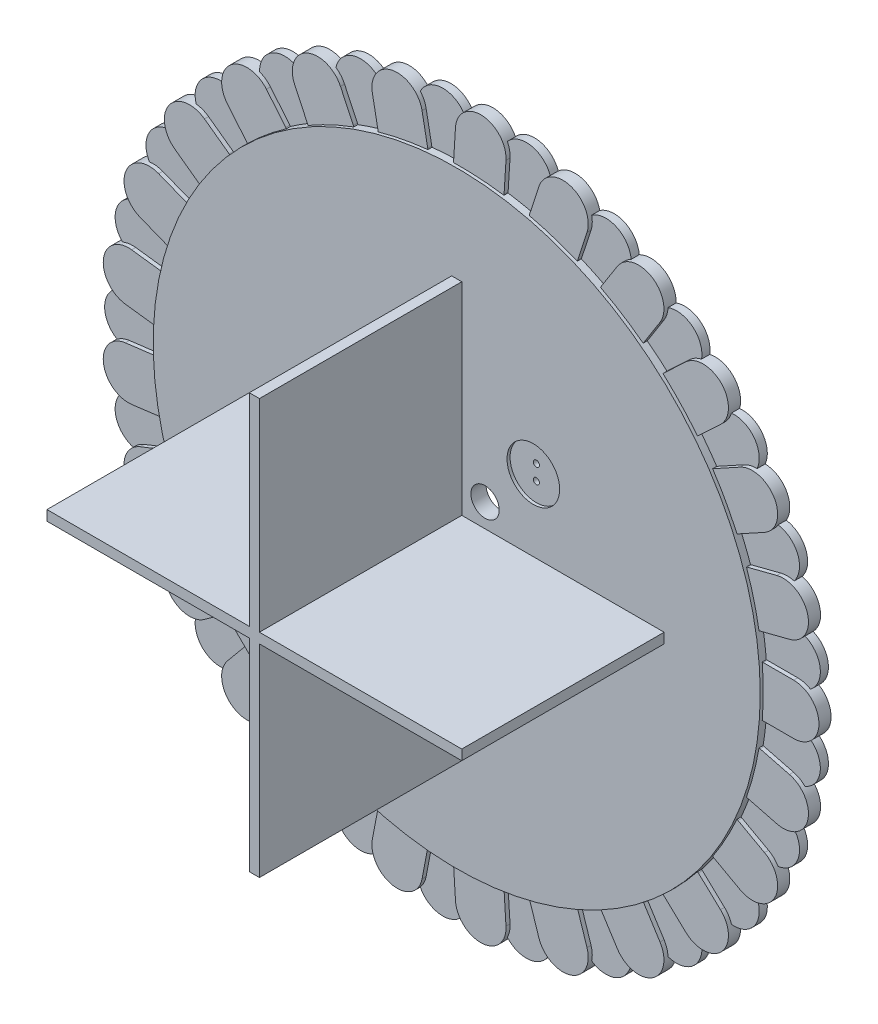
SolidWorks part; units mm, degrees
ref_plane "Front Plane" through (0, 0, 0) normal (0, 0, 1) x (1, 0, 0)
ref_plane "Top Plane" through (0, 0, 0) normal (0, 1, 0) x (1, 0, 0)
ref_plane "Right Plane" through (0, 0, 0) normal (1, 0, 0) x (0, 0, -1)
sketch "Schizzo1" plane through (0, 0, 0) normal (0, 0, 1) x (1, 0, 0)
  circle A0 centre (0, 0) radius 30
  dimension "D1" = 60
extrude "Estrusione-Estrusione1" add sketch "Schizzo1" along normal blind 1.5
sketch "Schizzo2" plane through (0, 0, 1.5) normal (0, 0, 1) x (1, 0, 0)
  line L0 (-0.5, 0.5) -> (-0.5, 20.5)
  line L1 (-20.5, 0.5) -> (-0.5, 0.5)
  line L2 (-20.5, 0.5) -> (-20.5, -0.5)
  line L3 (-20.5, -0.5) -> (-0.5, -0.5)
  line L4 (20.5, 0.5) -> (20.5, -0.5)
  line L5 (-0.5, 0.5) -> (0.5, -0.5) construction
  line L7 (0.5, -20.5) -> (-0.5, -20.5)
  line L8 (0.5, -20.5) -> (0.5, -0.5)
  line L9 (0.5, 20.5) -> (-0.5, 20.5)
  line L10 (-0.5, -20.5) -> (-0.5, -0.5)
  line L15 (0.5, 0.5) -> (0.5, 20.5)
  line L18 (0.5, 0.5) -> (20.5, 0.5)
  line L19 (0.5, -0.5) -> (20.5, -0.5)
  point P0 (0, 0)
  point P6 (0, 0)
  point P11 (0, 0)
  dimension "D1" = 20
  dimension "D2" = 1
extrude "Estrusione-Estrusione2" add sketch "Schizzo2" along normal blind 20
sketch "Schizzo3" plane through (0, 0, 1.5) normal (0, 0, 1) x (1, 0, 0)
  line L0 (-7.5711, 6.8211) -> (-7.5711, 8.3211) construction
  line L1 (-20.5, 0) -> (20.5, 0) construction
  line L2 (0.2363, -0.2363) -> (-0.5137, 0.5137) construction
  line L4 (-20.5, 0.5) -> (-20.5, -0.5) construction
  line L5 (20.5, -0.5) -> (20.5, 0.5) construction
  line L6 (0.5, 20.5) -> (-0.5, 20.5) construction
  line L7 (0, 20.5) -> (0, -20.5) construction
  line L8 (-0.5, -20.5) -> (0.5, -20.5) construction
  circle A0 centre (-7.5711, 8.3211) radius 0.3
  circle A1 centre (-7.5711, 6.8211) radius 0.3
  circle A3 centre (-7.5711, 7.5711) radius 2.5 construction
  circle A4 centre (-7.5711, -8.3211) radius 0.3
  circle A5 centre (-7.5711, -6.8211) radius 0.3
  circle A6 centre (-7.5711, -7.5711) radius 2.5 construction
  circle A7 centre (7.5711, -8.3211) radius 0.3
  circle A8 centre (7.5711, -7.5711) radius 2.5 construction
  circle A9 centre (7.5711, -6.8211) radius 0.3
  circle A10 centre (7.5711, 8.3211) radius 0.3
  circle A11 centre (7.5711, 6.8211) radius 0.3
  circle A12 centre (7.5711, 7.5711) radius 2.5 construction
  dimension "D1" = 1.5
  dimension "D2" = 0.6
  dimension "D3" = 5
  dimension "D4" = 10
extrude "Taglio-Estrusione1" cut sketch "Schizzo3" against normal through all contours A1 | A0 | A11 | A10 | A5 | A4 | A7 | A9 region at (-7.5711, 8.3211, 1.5) region at (-7.5711, 6.8211, 1.5) region at (-7.5711, -8.3211, 1.5) region at (-7.5711, -6.8211, 1.5) region at (7.5711, -8.3211, 1.5) region at (7.5711, -6.8211, 1.5) region at (7.5711, 8.3211, 1.5) region at (7.5711, 6.8211, 1.5)
sketch "Schizzo4" plane through (0, 0, 1.5) normal (0, 0, 1) x (1, 0, 0)
  line L0 (-7.5711, -6.8211) -> (-7.5711, -8.3211) construction
  line L1 (-20.5, 0) -> (-4.4705, 0) construction
  line L2 (-20.5, 0.5) -> (-20.5, -0.5) construction
  line L3 (0, -20.5) -> (0, -5.0355) construction
  line L4 (-0.5, -20.5) -> (0.5, -20.5) construction
  circle A0 centre (-7.5711, -7.5711) radius 2.6
  circle A1 centre (7.5711, -7.5711) radius 2.6
  circle A2 centre (7.5711, 7.5711) radius 2.6
  circle A3 centre (-7.5711, 7.5711) radius 2.6
  dimension "D1" = 5.2
extrude "Taglio-Estrusione2" cut sketch "Schizzo4" against normal blind 0.3
sketch "Schizzo5" plane through (0, 0, 0) normal (0, 0, -1) x (-1, 0, 0)
  line L0 (-30, 0) -> (-33, 0) construction
  line L1 (-30, -2.5) -> (-33, -2.5)
  line L2 (-30, 2.5) -> (-33, 2.5)
  line L3 (-29.4501, 6.2403) -> (-32.4265, 6.6163)
  line L4 (-30.0768, 1.2797) -> (-33.0531, 1.6557)
  line L5 (-29.7634, 3.76) -> (-32.7398, 4.136) construction
  line L6 (-28.4358, 9.8822) -> (-31.3415, 10.6282)
  line L7 (-29.6792, 5.0392) -> (-32.585, 5.7853)
  line L8 (-29.0575, 7.4607) -> (-31.9632, 8.2068) construction
  line L9 (-26.973, 13.3682) -> (-29.7623, 14.4726)
  line L10 (-28.8136, 8.7193) -> (-31.6029, 9.8237)
  line L11 (-27.8933, 11.0437) -> (-30.6826, 12.1481) construction
  line L12 (-25.0848, 16.6434) -> (-27.7137, 18.0886)
  line L13 (-27.4936, 12.2618) -> (-30.1225, 13.7071)
  line L14 (-26.2892, 14.4526) -> (-28.9181, 15.8979) construction
  line L15 (-22.801, 19.6561) -> (-25.2281, 21.4195)
  line L16 (-25.74, 15.611) -> (-28.167, 17.3744)
  line L17 (-24.2705, 17.6336) -> (-26.6976, 19.3969) construction
  line L18 (-20.1577, 22.3588) -> (-22.3446, 24.4125)
  line L19 (-23.5804, 18.714) -> (-25.7673, 20.7676)
  line L20 (-21.8691, 20.5364) -> (-24.056, 22.5901) construction
  line L21 (-17.1964, 24.709) -> (-19.1087, 27.0205)
  line L22 (-21.049, 21.5218) -> (-22.9613, 23.8334)
  line L23 (-19.1227, 23.1154) -> (-21.035, 25.4269) construction
  line L24 (-13.964, 26.6694) -> (-15.5715, 29.2024)
  line L25 (-18.1856, 23.9903) -> (-19.7931, 26.5233)
  line L26 (-16.0748, 25.3298) -> (-17.6823, 27.8628) construction
  line L27 (-10.5113, 28.2093) -> (-11.7886, 30.9237)
  line L28 (-15.0354, 26.0804) -> (-16.3128, 28.7948)
  line L29 (-12.7734, 27.1448) -> (-14.0507, 29.8593) construction
  line L30 (-6.8929, 29.3042) -> (-7.8199, 32.1574)
  line L31 (-11.6482, 27.7592) -> (-12.5752, 30.6123)
  line L32 (-9.2705, 28.5317) -> (-10.1976, 31.3849) construction
  line L33 (-3.1657, 29.9371) -> (-3.7279, 32.8839)
  line L34 (-8.0772, 29.0002) -> (-8.6393, 31.947)
  line L35 (-5.6214, 29.4686) -> (-6.1836, 32.4155) construction
  line L36 (0.6114, 30.0978) -> (0.423, 33.0919)
  line L37 (-4.3788, 29.7838) -> (-4.5672, 32.7779)
  line L38 (-1.8837, 29.9408) -> (-2.0721, 32.9349) construction
  line L39 (4.3788, 29.7838) -> (4.5672, 32.7779)
  line L40 (-0.6114, 30.0978) -> (-0.423, 33.0919)
  line L41 (1.8837, 29.9408) -> (2.0721, 32.9349) construction
  line L42 (8.0772, 29.0002) -> (8.6393, 31.947)
  line L43 (3.1657, 29.9371) -> (3.7279, 32.8839)
  line L44 (5.6214, 29.4686) -> (6.1836, 32.4155) construction
  line L45 (11.6482, 27.7592) -> (12.5752, 30.6123)
  line L46 (6.8929, 29.3042) -> (7.8199, 32.1574)
  line L47 (9.2705, 28.5317) -> (10.1976, 31.3849) construction
  line L48 (15.0354, 26.0804) -> (16.3128, 28.7948)
  line L49 (10.5113, 28.2093) -> (11.7886, 30.9237)
  line L50 (12.7734, 27.1448) -> (14.0507, 29.8593) construction
  line L51 (18.1856, 23.9903) -> (19.7931, 26.5233)
  line L52 (13.964, 26.6694) -> (15.5715, 29.2024)
  line L53 (16.0748, 25.3298) -> (17.6823, 27.8628) construction
  line L54 (21.049, 21.5218) -> (22.9613, 23.8334)
  line L55 (17.1964, 24.709) -> (19.1087, 27.0205)
  line L56 (19.1227, 23.1154) -> (21.035, 25.4269) construction
  line L57 (23.5804, 18.714) -> (25.7673, 20.7676)
  line L58 (20.1577, 22.3588) -> (22.3446, 24.4125)
  line L59 (21.8691, 20.5364) -> (24.056, 22.5901) construction
  line L60 (25.74, 15.611) -> (28.167, 17.3744)
  line L61 (22.801, 19.6561) -> (25.2281, 21.4195)
  line L62 (24.2705, 17.6336) -> (26.6976, 19.3969) construction
  line L63 (27.4936, 12.2618) -> (30.1225, 13.7071)
  line L64 (25.0848, 16.6434) -> (27.7137, 18.0886)
  line L65 (26.2892, 14.4526) -> (28.9181, 15.8979) construction
  line L66 (28.8136, 8.7193) -> (31.6029, 9.8237)
  line L67 (26.973, 13.3682) -> (29.7623, 14.4726)
  line L68 (27.8933, 11.0437) -> (30.6826, 12.1481) construction
  line L69 (29.6792, 5.0392) -> (32.585, 5.7853)
  line L70 (28.4358, 9.8822) -> (31.3415, 10.6282)
  line L71 (29.0575, 7.4607) -> (31.9632, 8.2068) construction
  line L72 (30.0768, 1.2797) -> (33.0531, 1.6557)
  line L73 (29.4501, 6.2403) -> (32.4265, 6.6163)
  line L74 (29.7634, 3.76) -> (32.7398, 4.136) construction
  line L75 (30, -2.5) -> (33, -2.5)
  line L76 (30, 2.5) -> (33, 2.5)
  line L77 (30, 0) -> (33, 0) construction
  line L78 (29.4501, -6.2403) -> (32.4265, -6.6163)
  line L79 (30.0768, -1.2797) -> (33.0531, -1.6557)
  line L80 (29.7634, -3.76) -> (32.7398, -4.136) construction
  line L81 (28.4358, -9.8822) -> (31.3415, -10.6282)
  line L82 (29.6792, -5.0392) -> (32.585, -5.7853)
  line L83 (29.0575, -7.4607) -> (31.9632, -8.2068) construction
  line L84 (26.973, -13.3682) -> (29.7623, -14.4726)
  line L85 (28.8136, -8.7193) -> (31.6029, -9.8237)
  line L86 (27.8933, -11.0437) -> (30.6826, -12.1481) construction
  line L87 (25.0848, -16.6434) -> (27.7137, -18.0886)
  line L88 (27.4936, -12.2618) -> (30.1225, -13.7071)
  line L89 (26.2892, -14.4526) -> (28.9181, -15.8979) construction
  line L90 (22.801, -19.6561) -> (25.2281, -21.4195)
  line L91 (25.74, -15.611) -> (28.167, -17.3744)
  line L92 (24.2705, -17.6336) -> (26.6976, -19.3969) construction
  line L93 (20.1577, -22.3588) -> (22.3446, -24.4125)
  line L94 (23.5804, -18.714) -> (25.7673, -20.7676)
  line L95 (21.8691, -20.5364) -> (24.056, -22.5901) construction
  line L96 (17.1964, -24.709) -> (19.1087, -27.0205)
  line L97 (21.049, -21.5218) -> (22.9613, -23.8334)
  line L98 (19.1227, -23.1154) -> (21.035, -25.4269) construction
  line L99 (13.964, -26.6694) -> (15.5715, -29.2024)
  line L100 (18.1856, -23.9903) -> (19.7931, -26.5233)
  line L101 (16.0748, -25.3298) -> (17.6823, -27.8628) construction
  line L102 (10.5113, -28.2093) -> (11.7886, -30.9237)
  line L103 (15.0354, -26.0804) -> (16.3128, -28.7948)
  line L104 (12.7734, -27.1448) -> (14.0507, -29.8593) construction
  line L105 (6.8929, -29.3042) -> (7.8199, -32.1574)
  line L106 (11.6482, -27.7592) -> (12.5752, -30.6123)
  line L107 (9.2705, -28.5317) -> (10.1976, -31.3849) construction
  line L108 (3.1657, -29.9371) -> (3.7279, -32.8839)
  line L109 (8.0772, -29.0002) -> (8.6393, -31.947)
  line L110 (5.6214, -29.4686) -> (6.1836, -32.4155) construction
  line L111 (-0.6114, -30.0978) -> (-0.423, -33.0919)
  line L112 (4.3788, -29.7838) -> (4.5672, -32.7779)
  line L113 (1.8837, -29.9408) -> (2.0721, -32.9349) construction
  line L114 (-4.3788, -29.7838) -> (-4.5672, -32.7779)
  line L115 (0.6114, -30.0978) -> (0.423, -33.0919)
  line L116 (-1.8837, -29.9408) -> (-2.0721, -32.9349) construction
  line L117 (-8.0772, -29.0002) -> (-8.6393, -31.947)
  line L118 (-3.1657, -29.9371) -> (-3.7279, -32.8839)
  line L119 (-5.6214, -29.4686) -> (-6.1836, -32.4155) construction
  line L120 (-11.6482, -27.7592) -> (-12.5752, -30.6123)
  line L121 (-6.8929, -29.3042) -> (-7.8199, -32.1574)
  line L122 (-9.2705, -28.5317) -> (-10.1976, -31.3849) construction
  line L123 (-15.0354, -26.0804) -> (-16.3128, -28.7948)
  line L124 (-10.5113, -28.2093) -> (-11.7886, -30.9237)
  line L125 (-12.7734, -27.1448) -> (-14.0507, -29.8593) construction
  line L126 (-18.1856, -23.9903) -> (-19.7931, -26.5233)
  line L127 (-13.964, -26.6694) -> (-15.5715, -29.2024)
  line L128 (-16.0748, -25.3298) -> (-17.6823, -27.8628) construction
  line L129 (-21.049, -21.5218) -> (-22.9613, -23.8334)
  line L130 (-17.1964, -24.709) -> (-19.1087, -27.0205)
  line L131 (-19.1227, -23.1154) -> (-21.035, -25.4269) construction
  line L132 (-23.5804, -18.714) -> (-25.7673, -20.7676)
  line L133 (-20.1577, -22.3588) -> (-22.3446, -24.4125)
  line L134 (-21.8691, -20.5364) -> (-24.056, -22.5901) construction
  line L135 (-25.74, -15.611) -> (-28.167, -17.3744)
  line L136 (-22.801, -19.6561) -> (-25.2281, -21.4195)
  line L137 (-24.2705, -17.6336) -> (-26.6976, -19.3969) construction
  line L138 (-27.4936, -12.2618) -> (-30.1225, -13.7071)
  line L139 (-25.0848, -16.6434) -> (-27.7137, -18.0886)
  line L140 (-26.2892, -14.4526) -> (-28.9181, -15.8979) construction
  line L141 (-28.8136, -8.7193) -> (-31.6029, -9.8237)
  line L142 (-26.973, -13.3682) -> (-29.7623, -14.4726)
  line L143 (-27.8933, -11.0437) -> (-30.6826, -12.1481) construction
  line L144 (-29.6792, -5.0392) -> (-32.585, -5.7853)
  line L145 (-28.4358, -9.8822) -> (-31.3415, -10.6282)
  line L146 (-29.0575, -7.4607) -> (-31.9632, -8.2068) construction
  line L147 (-30.0768, -1.2797) -> (-33.0531, -1.6557)
  line L148 (-29.4501, -6.2403) -> (-32.4265, -6.6163)
  line L149 (-29.7634, -3.76) -> (-32.7398, -4.136) construction
  circle A0 centre (0, 0) radius 30 construction
  arc A1 (-30, -2.5) -> (-30, 2.5) centre (-30, 0) ccw
  arc A2 (-33, 2.5) -> (-33, -2.5) centre (-33, 0) ccw
  arc A3 (-30.0768, 1.2797) -> (-29.4501, 6.2403) centre (-29.7634, 3.76) ccw
  arc A4 (-32.4265, 6.6163) -> (-33.0531, 1.6557) centre (-32.7398, 4.136) ccw
  arc A5 (-29.6792, 5.0392) -> (-28.4358, 9.8822) centre (-29.0575, 7.4607) ccw
  arc A6 (-31.3415, 10.6282) -> (-32.585, 5.7853) centre (-31.9632, 8.2068) ccw
  arc A7 (-28.8136, 8.7193) -> (-26.973, 13.3682) centre (-27.8933, 11.0437) ccw
  arc A8 (-29.7623, 14.4726) -> (-31.6029, 9.8237) centre (-30.6826, 12.1481) ccw
  arc A9 (-27.4936, 12.2618) -> (-25.0848, 16.6434) centre (-26.2892, 14.4526) ccw
  arc A10 (-27.7137, 18.0886) -> (-30.1225, 13.7071) centre (-28.9181, 15.8979) ccw
  arc A11 (-25.74, 15.611) -> (-22.801, 19.6561) centre (-24.2705, 17.6336) ccw
  arc A12 (-25.2281, 21.4195) -> (-28.167, 17.3744) centre (-26.6976, 19.3969) ccw
  arc A13 (-23.5804, 18.714) -> (-20.1577, 22.3588) centre (-21.8691, 20.5364) ccw
  arc A14 (-22.3446, 24.4125) -> (-25.7673, 20.7676) centre (-24.056, 22.5901) ccw
  arc A15 (-21.049, 21.5218) -> (-17.1964, 24.709) centre (-19.1227, 23.1154) ccw
  arc A16 (-19.1087, 27.0205) -> (-22.9613, 23.8334) centre (-21.035, 25.4269) ccw
  arc A17 (-18.1856, 23.9903) -> (-13.964, 26.6694) centre (-16.0748, 25.3298) ccw
  arc A18 (-15.5715, 29.2024) -> (-19.7931, 26.5233) centre (-17.6823, 27.8628) ccw
  arc A19 (-15.0354, 26.0804) -> (-10.5113, 28.2093) centre (-12.7734, 27.1448) ccw
  arc A20 (-11.7886, 30.9237) -> (-16.3128, 28.7948) centre (-14.0507, 29.8593) ccw
  arc A21 (-11.6482, 27.7592) -> (-6.8929, 29.3042) centre (-9.2705, 28.5317) ccw
  arc A22 (-7.8199, 32.1574) -> (-12.5752, 30.6123) centre (-10.1976, 31.3849) ccw
  arc A23 (-8.0772, 29.0002) -> (-3.1657, 29.9371) centre (-5.6214, 29.4686) ccw
  arc A24 (-3.7279, 32.8839) -> (-8.6393, 31.947) centre (-6.1836, 32.4155) ccw
  arc A25 (-4.3788, 29.7838) -> (0.6114, 30.0978) centre (-1.8837, 29.9408) ccw
  arc A26 (0.423, 33.0919) -> (-4.5672, 32.7779) centre (-2.0721, 32.9349) ccw
  arc A27 (-0.6114, 30.0978) -> (4.3788, 29.7838) centre (1.8837, 29.9408) ccw
  arc A28 (4.5672, 32.7779) -> (-0.423, 33.0919) centre (2.0721, 32.9349) ccw
  arc A29 (3.1657, 29.9371) -> (8.0772, 29.0002) centre (5.6214, 29.4686) ccw
  arc A30 (8.6393, 31.947) -> (3.7279, 32.8839) centre (6.1836, 32.4155) ccw
  arc A31 (6.8929, 29.3042) -> (11.6482, 27.7592) centre (9.2705, 28.5317) ccw
  arc A32 (12.5752, 30.6123) -> (7.8199, 32.1574) centre (10.1976, 31.3849) ccw
  arc A33 (10.5113, 28.2093) -> (15.0354, 26.0804) centre (12.7734, 27.1448) ccw
  arc A34 (16.3128, 28.7948) -> (11.7886, 30.9237) centre (14.0507, 29.8593) ccw
  arc A35 (13.964, 26.6694) -> (18.1856, 23.9903) centre (16.0748, 25.3298) ccw
  arc A36 (19.7931, 26.5233) -> (15.5715, 29.2024) centre (17.6823, 27.8628) ccw
  arc A37 (17.1964, 24.709) -> (21.049, 21.5218) centre (19.1227, 23.1154) ccw
  arc A38 (22.9613, 23.8334) -> (19.1087, 27.0205) centre (21.035, 25.4269) ccw
  arc A39 (20.1577, 22.3588) -> (23.5804, 18.714) centre (21.8691, 20.5364) ccw
  arc A40 (25.7673, 20.7676) -> (22.3446, 24.4125) centre (24.056, 22.5901) ccw
  arc A41 (22.801, 19.6561) -> (25.74, 15.611) centre (24.2705, 17.6336) ccw
  arc A42 (28.167, 17.3744) -> (25.2281, 21.4195) centre (26.6976, 19.3969) ccw
  arc A43 (25.0848, 16.6434) -> (27.4936, 12.2618) centre (26.2892, 14.4526) ccw
  arc A44 (30.1225, 13.7071) -> (27.7137, 18.0886) centre (28.9181, 15.8979) ccw
  arc A45 (26.973, 13.3682) -> (28.8136, 8.7193) centre (27.8933, 11.0437) ccw
  arc A46 (31.6029, 9.8237) -> (29.7623, 14.4726) centre (30.6826, 12.1481) ccw
  arc A47 (28.4358, 9.8822) -> (29.6792, 5.0392) centre (29.0575, 7.4607) ccw
  arc A48 (32.585, 5.7853) -> (31.3415, 10.6282) centre (31.9632, 8.2068) ccw
  arc A49 (29.4501, 6.2403) -> (30.0768, 1.2797) centre (29.7634, 3.76) ccw
  arc A50 (33.0531, 1.6557) -> (32.4265, 6.6163) centre (32.7398, 4.136) ccw
  arc A51 (30, 2.5) -> (30, -2.5) centre (30, 0) ccw
  arc A52 (33, -2.5) -> (33, 2.5) centre (33, 0) ccw
  arc A53 (30.0768, -1.2797) -> (29.4501, -6.2403) centre (29.7634, -3.76) ccw
  arc A54 (32.4265, -6.6163) -> (33.0531, -1.6557) centre (32.7398, -4.136) ccw
  arc A55 (29.6792, -5.0392) -> (28.4358, -9.8822) centre (29.0575, -7.4607) ccw
  arc A56 (31.3415, -10.6282) -> (32.585, -5.7853) centre (31.9632, -8.2068) ccw
  arc A57 (28.8136, -8.7193) -> (26.973, -13.3682) centre (27.8933, -11.0437) ccw
  arc A58 (29.7623, -14.4726) -> (31.6029, -9.8237) centre (30.6826, -12.1481) ccw
  arc A59 (27.4936, -12.2618) -> (25.0848, -16.6434) centre (26.2892, -14.4526) ccw
  arc A60 (27.7137, -18.0886) -> (30.1225, -13.7071) centre (28.9181, -15.8979) ccw
  arc A61 (25.74, -15.611) -> (22.801, -19.6561) centre (24.2705, -17.6336) ccw
  arc A62 (25.2281, -21.4195) -> (28.167, -17.3744) centre (26.6976, -19.3969) ccw
  arc A63 (23.5804, -18.714) -> (20.1577, -22.3588) centre (21.8691, -20.5364) ccw
  arc A64 (22.3446, -24.4125) -> (25.7673, -20.7676) centre (24.056, -22.5901) ccw
  arc A65 (21.049, -21.5218) -> (17.1964, -24.709) centre (19.1227, -23.1154) ccw
  arc A66 (19.1087, -27.0205) -> (22.9613, -23.8334) centre (21.035, -25.4269) ccw
  arc A67 (18.1856, -23.9903) -> (13.964, -26.6694) centre (16.0748, -25.3298) ccw
  arc A68 (15.5715, -29.2024) -> (19.7931, -26.5233) centre (17.6823, -27.8628) ccw
  arc A69 (15.0354, -26.0804) -> (10.5113, -28.2093) centre (12.7734, -27.1448) ccw
  arc A70 (11.7886, -30.9237) -> (16.3128, -28.7948) centre (14.0507, -29.8593) ccw
  arc A71 (11.6482, -27.7592) -> (6.8929, -29.3042) centre (9.2705, -28.5317) ccw
  arc A72 (7.8199, -32.1574) -> (12.5752, -30.6123) centre (10.1976, -31.3849) ccw
  arc A73 (8.0772, -29.0002) -> (3.1657, -29.9371) centre (5.6214, -29.4686) ccw
  arc A74 (3.7279, -32.8839) -> (8.6393, -31.947) centre (6.1836, -32.4155) ccw
  arc A75 (4.3788, -29.7838) -> (-0.6114, -30.0978) centre (1.8837, -29.9408) ccw
  arc A76 (-0.423, -33.0919) -> (4.5672, -32.7779) centre (2.0721, -32.9349) ccw
  arc A77 (0.6114, -30.0978) -> (-4.3788, -29.7838) centre (-1.8837, -29.9408) ccw
  arc A78 (-4.5672, -32.7779) -> (0.423, -33.0919) centre (-2.0721, -32.9349) ccw
  arc A79 (-3.1657, -29.9371) -> (-8.0772, -29.0002) centre (-5.6214, -29.4686) ccw
  arc A80 (-8.6393, -31.947) -> (-3.7279, -32.8839) centre (-6.1836, -32.4155) ccw
  arc A81 (-6.8929, -29.3042) -> (-11.6482, -27.7592) centre (-9.2705, -28.5317) ccw
  arc A82 (-12.5752, -30.6123) -> (-7.8199, -32.1574) centre (-10.1976, -31.3849) ccw
  arc A83 (-10.5113, -28.2093) -> (-15.0354, -26.0804) centre (-12.7734, -27.1448) ccw
  arc A84 (-16.3128, -28.7948) -> (-11.7886, -30.9237) centre (-14.0507, -29.8593) ccw
  arc A85 (-13.964, -26.6694) -> (-18.1856, -23.9903) centre (-16.0748, -25.3298) ccw
  arc A86 (-19.7931, -26.5233) -> (-15.5715, -29.2024) centre (-17.6823, -27.8628) ccw
  arc A87 (-17.1964, -24.709) -> (-21.049, -21.5218) centre (-19.1227, -23.1154) ccw
  arc A88 (-22.9613, -23.8334) -> (-19.1087, -27.0205) centre (-21.035, -25.4269) ccw
  arc A89 (-20.1577, -22.3588) -> (-23.5804, -18.714) centre (-21.8691, -20.5364) ccw
  arc A90 (-25.7673, -20.7676) -> (-22.3446, -24.4125) centre (-24.056, -22.5901) ccw
  arc A91 (-22.801, -19.6561) -> (-25.74, -15.611) centre (-24.2705, -17.6336) ccw
  arc A92 (-28.167, -17.3744) -> (-25.2281, -21.4195) centre (-26.6976, -19.3969) ccw
  arc A93 (-25.0848, -16.6434) -> (-27.4936, -12.2618) centre (-26.2892, -14.4526) ccw
  arc A94 (-30.1225, -13.7071) -> (-27.7137, -18.0886) centre (-28.9181, -15.8979) ccw
  arc A95 (-26.973, -13.3682) -> (-28.8136, -8.7193) centre (-27.8933, -11.0437) ccw
  arc A96 (-31.6029, -9.8237) -> (-29.7623, -14.4726) centre (-30.6826, -12.1481) ccw
  arc A97 (-28.4358, -9.8822) -> (-29.6792, -5.0392) centre (-29.0575, -7.4607) ccw
  arc A98 (-32.585, -5.7853) -> (-31.3415, -10.6282) centre (-31.9632, -8.2068) ccw
  arc A99 (-29.4501, -6.2403) -> (-30.0768, -1.2797) centre (-29.7634, -3.76) ccw
  arc A100 (-33.0531, -1.6557) -> (-32.4265, -6.6163) centre (-32.7398, -4.136) ccw
  point P6 (-31.5, 0)
  point P11 (0, 0)
  point P12 (0, 0)
  point P16 (-31.2516, 3.948)
  point P23 (-30.5104, 7.8337)
  point P30 (-29.288, 11.5959)
  point P37 (-27.6037, 15.1752)
  point P44 (-25.484, 18.5152)
  point P51 (-22.9625, 21.5632)
  point P58 (-20.0789, 24.2712)
  point P65 (-16.8785, 26.5963)
  point P72 (-13.412, 28.5021)
  point P79 (-9.734, 29.9583)
  point P86 (-5.9025, 30.942)
  point P93 (-1.9779, 31.4378)
  point P100 (1.9779, 31.4378)
  point P107 (5.9025, 30.942)
  point P114 (9.734, 29.9583)
  point P121 (13.412, 28.5021)
  point P128 (16.8785, 26.5963)
  point P135 (20.0789, 24.2712)
  point P142 (22.9625, 21.5632)
  point P149 (25.484, 18.5152)
  point P156 (27.6037, 15.1752)
  point P163 (29.288, 11.5959)
  point P170 (30.5104, 7.8337)
  point P177 (31.2516, 3.948)
  point P184 (31.5, 0)
  point P191 (31.2516, -3.948)
  point P198 (30.5104, -7.8337)
  point P205 (29.288, -11.5959)
  point P212 (27.6037, -15.1752)
  point P219 (25.484, -18.5152)
  point P226 (22.9625, -21.5632)
  point P233 (20.0789, -24.2712)
  point P240 (16.8785, -26.5963)
  point P247 (13.412, -28.5021)
  point P254 (9.734, -29.9583)
  point P261 (5.9025, -30.942)
  point P268 (1.9779, -31.4378)
  point P275 (-1.9779, -31.4378)
  point P282 (-5.9025, -30.942)
  point P289 (-9.734, -29.9583)
  point P296 (-13.412, -28.5021)
  point P303 (-16.8785, -26.5963)
  point P310 (-20.0789, -24.2712)
  point P317 (-22.9625, -21.5632)
  point P324 (-25.484, -18.5152)
  point P331 (-27.6037, -15.1752)
  point P338 (-29.288, -11.5959)
  point P345 (-30.5104, -7.8337)
  point P352 (-31.2516, -3.948)
  point P357 (0, 0)
  circle M206 centre (0, 0) radius 30
  dimension "D1" = 5
  dimension "D2" = 3
  dimension "D4" = 4.136
  dimension "D5" = 0.2602
  dimension "D3" = 50
extrude "Estrusione-Estrusione3" add sketch "Schizzo5" against normal blind 0.8 contours A6 A4 A2 L2 A1 A5 L7 M206 | A10 A8 A6 L6 A5 A9 L13 M206 | A14 A12 A10 L12 A9 A13 L19 M206 | A18 A16 A14 L18 A13 A17 L25 M206 | A22 A20 A18 L24 A17 A21 L31 M206 | A26 A24 A22 L30 A21 A25 L37 M206 | A30 A28 A26 L36 A25 A29 L43 M206 | A34 A32 A30 L42 A29 A33 L49 M206 | A38 A36 A34 L48 A33 A37 L55 M206 | A42 A40 A38 L54 A37 A41 L61 M206 | A46 A44 A42 L60 A41 A45 L67 M206 | A50 A48 A46 L66 A45 A49 L73 M206 | A54 A52 A50 L72 A49 A53 L79 M206 | A58 A56 A54 L78 A53 A57 L85 M206 | A62 A60 A58 L84 A57 A61 L91 M206 | A66 A64 A62 L90 A61 A65 L97 M206 | A70 A68 A66 L96 A65 A69 L103 M206 | A74 A72 A70 L102 A69 A73 L109 M206 | A78 A76 A74 L108 A73 A77 L115 M206 | A82 A80 A78 L114 A77 A81 L121 M206 | A86 A84 A82 L120 A81 A85 L127 M206 | A90 A88 A86 L126 A85 A89 L133 M206 | A94 A92 A90 L132 A89 A93 L139 M206 | A98 A96 A94 L138 A93 A97 L145 M206 | A2 A100 A98 L144 A97 A1 L1 M206 region at (32.5734, -4.115, 0) region at (32.5734, 4.115, 0) region at (30.5267, -12.0864, 0) region at (30.5267, 12.0864, 0) region at (26.5619, -19.2983, 0) region at (26.5619, 19.2983, 0) region at (20.9281, -25.2977, 0) region at (20.9281, 25.2977, 0) region at (13.9793, -29.7075, 0) region at (13.9793, 29.7075, 0) region at (6.1522, -32.2507, 0) region at (6.1522, 32.2507, 0) region at (-2.0616, -32.7675, 0) region at (-2.0616, 32.7675, 0) region at (-10.1457, -31.2254, 0) region at (-10.1457, 31.2254, 0) region at (-17.5924, -27.7212, 0) region at (-17.5924, 27.7212, 0) region at (-23.9337, -22.4752, 0) region at (-23.9337, 22.4752, 0) region at (-28.7711, -15.8171, 0) region at (-28.7711, 15.8171, 0) region at (-31.8008, -8.1651, 0) region at (-31.8008, 8.1651, 0) region at (-32.8323, 0, 0)
extrude "Estrusione-Estrusione4" add sketch "Schizzo5<3>" against normal blind 1.2 contours A9 L12 A10 L13 | A13 L18 A14 L19 | A17 L24 A18 L25 | A21 L30 A22 L31 | A25 L36 A26 L37 | A29 L42 A30 L43 | A33 L48 A34 L49 | A37 L54 A38 L55 | A41 L60 A42 L61 | A45 L66 A46 L67 | A49 L72 A50 L73 | A53 L78 A54 L79 | A57 L84 A58 L85 | A61 L90 A62 L91 | A65 L96 A66 L97 | A69 L102 A70 L103 | A73 L108 A74 L109 | A77 L114 A78 L115 | A81 L120 A82 L121 | A85 L126 A86 L127 | A89 L132 A90 L133 | A93 L138 A94 L139 | A97 L144 A98 L145 | A1 L2 A2 L1 | A5 L6 A6 L7
sketch "Schizzo5<3>" plane through (0, 0, 0) normal (0, 0, -1) x (-1, 0, 0) same geometry as "Schizzo5"
sketch "Schizzo6" plane through (0, 0, 1.5) normal (0, 0, 1) x (1, 0, 0)
  line L0 (-22.5607, 0) -> (21.4273, 0) construction
  line L1 (0, 12.6583) -> (0, -8.7601) construction
  circle A0 centre (-2.8, 2.8) radius 1.4
  circle A1 centre (-2.8, -2.8) radius 1.4
  circle A2 centre (2.8, -2.8) radius 1.4
  circle A3 centre (2.8, 2.8) radius 1.4
  dimension "D3" = 2.8
  dimension "D1" = 2.8
  dimension "D2" = 2.8
extrude "Taglio-Estrusione3" cut sketch "Schizzo6" against normal through all
